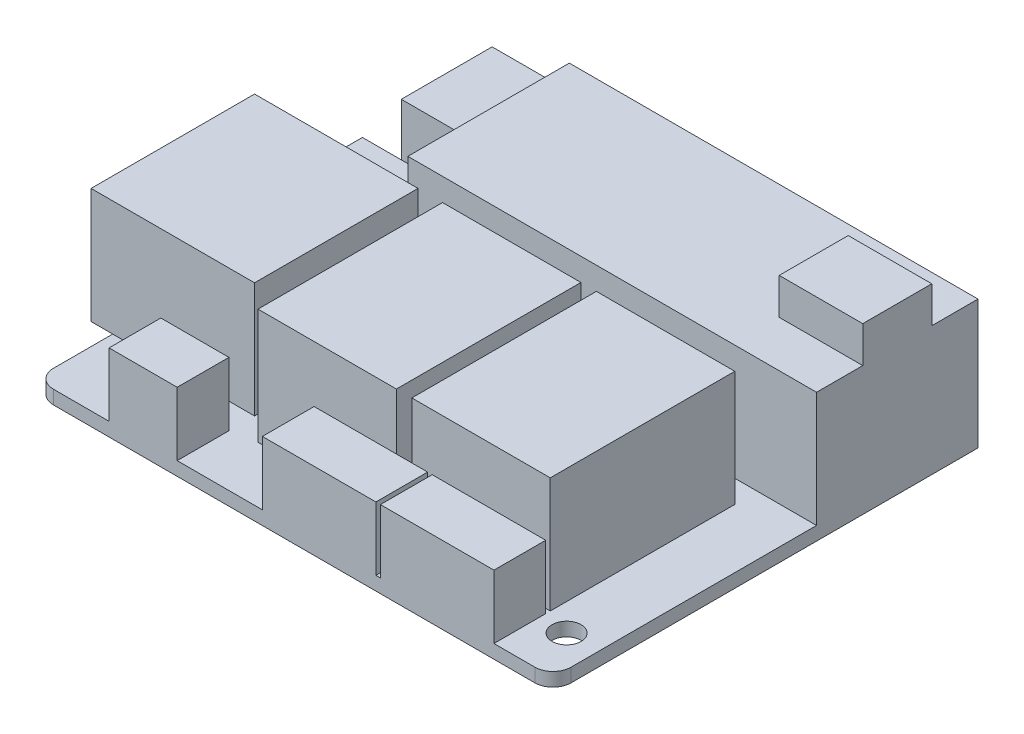
SolidWorks part; units mm, degrees
ref_plane "Front plane" through (0, 0, 0) normal (0, 0, 1) x (1, 0, 0)
ref_plane "Top plane" through (0, 0, 0) normal (0, 1, 0) x (1, 0, 0)
ref_plane "Right Plane" through (0, 0, 0) normal (1, 0, 0) x (0, 0, -1)
sketch "Sketch1" plane through (0, 0, 0) normal (0, 1, 0) x (1, 0, 0)
  line L1 (0, 0) -> (45, 0)
  line L2 (0, 0) -> (0, 17.78)
  line L3 (0, 17.78) -> (45, 17.78)
  line L4 (45, 0) -> (45, 17.78)
  line L5 (38.5, -22.82) -> (23.26, -22.82)
  line L6 (38.5, -22.82) -> (38.5, -2.5)
  line L7 (38.5, -2.5) -> (23.26, -2.5)
  line L8 (23.26, -22.82) -> (23.26, -2.5)
  line L9 (21.56, -22.82) -> (6.32, -22.82)
  line L10 (21.56, -22.82) -> (21.56, -2.5)
  line L11 (21.56, -2.5) -> (6.32, -2.5)
  line L12 (6.32, -22.82) -> (6.32, -2.5)
  line L13 (3.62, -2.5) -> (-14.38, -2.5)
  line L14 (3.62, -2.5) -> (3.62, -20.5)
  line L15 (3.62, -20.5) -> (-14.38, -20.5)
  line L16 (-14.38, -2.5) -> (-14.38, -20.5)
  dimension "D1" = 45
  dimension "D2" = 17.78
  dimension "D3" = 1.7
  dimension "D4" = 2.5
  dimension "D5" = 6.5
  dimension "D6" = 20.32
  dimension "D7" = 15.24
  dimension "D8" = 18
  dimension "D9" = 2.7
extrude "Boss-Extrude1" add sketch "Sketch1" along normal blind 12.7
sketch "Sketch2" plane through (0, 0, 0) normal (0, 1, 0) x (1, 0, 0)
  line L5 (38.5, -22.82) -> (38.5, -2.5) construction
  line L6 (38.5, -23.32) -> (26, -23.32)
  line L7 (38.5, -23.32) -> (38.5, -29.02)
  line L8 (38.5, -29.02) -> (26, -29.02)
  line L9 (26, -23.32) -> (26, -29.02)
  line L10 (25.5, -23.32) -> (13, -23.32)
  line L11 (25.5, -23.32) -> (25.5, -29.02)
  line L12 (25.5, -29.02) -> (13, -29.02)
  line L13 (13, -23.32) -> (13, -29.02)
  line L14 (23.26, -22.82) -> (38.5, -22.82) construction
  line L36 (3.62, -20.5) -> (3.62, -2.5) construction
  line L37 (3.62, -23.32) -> (-3.88, -23.32)
  line L38 (3.62, -23.32) -> (3.62, -29.02)
  line L39 (3.62, -29.02) -> (-3.88, -29.02)
  line L40 (-3.88, -23.32) -> (-3.88, -29.02)
  dimension "D1" = 5.7
  dimension "D2" = 7.5
  dimension "D3" = 0.5
  dimension "D4" = 12.5
  dimension "D5" = 0.5
extrude "Boss-Extrude2" add sketch "Sketch2" along normal blind 7 separate body
sketch "Sketch4" plane through (0, 0, 0) normal (0, 1, 0) x (1, 0, 0)
  line L0 (0, 17.78) -> (0, 0) construction
  line L1 (-3, 7) -> (-12, 7)
  line L2 (-3, 7) -> (-3, -20.5)
  line L3 (-3, -20.5) -> (-12, -20.5)
  line L4 (-12, 7) -> (-12, -20.5)
  line L8 (-14.38, -20.5) -> (3.62, -20.5) construction
  dimension "D1" = 27.5
  dimension "D2" = 12
  dimension "D3" = 9
extrude "Boss-Extrude4" add sketch "Sketch4" along normal blind 5 separate body
sketch "Sketch5" plane through (0, 0, 0) normal (0, 1, 0) x (1, 0, 0)
  line L1 (-1, 17.78) -> (-8.5, 17.78)
  line L2 (-1, 17.78) -> (-1, 7.78)
  line L3 (-1, 7.78) -> (-8.5, 7.78)
  line L4 (-8.5, 17.78) -> (-8.5, 7.78)
  line L8 (0, 17.78) -> (0, 0) construction
  line L9 (45, 17.78) -> (0, 17.78) construction
  dimension "D1" = 7.5
  dimension "D2" = 10
  dimension "D4" = 1
extrude "Boss-Extrude5" add sketch "Sketch5" along normal blind 10 separate body
sketch "Sketch3" plane through (0, 0, 0) normal (0, 1, 0) x (1, 0, 0)
  line L1 (45, 17.78) -> (-12, 17.78)
  line L2 (45, 17.78) -> (45, -29.02)
  line L3 (45, -29.02) -> (-12, -29.02)
  line L4 (-12, 17.78) -> (-12, -29.02)
  line L8 (-12, 7) -> (-12, -20.5) construction
  line L10 (26, -29.02) -> (38.5, -29.02) construction
  line L11 (45, 17.78) -> (0, 17.78) construction
  line L12 (45, 0) -> (45, 17.78) construction
  line L13 (18.5, 8.48) -> (41.5, 8.48) construction
  circle A0 centre (41.5, -24.02) radius 1.6
  circle A1 centre (41.5, 8.48) radius 1.6
  circle A2 centre (18.5, 8.48) radius 1.6
  dimension "D2" = 3.2
  dimension "D1" = 37.5
  dimension "D3" = 3.5
  dimension "D4" = 23
  dimension "D5" = 5
extrude "Boss-Extrude3" add sketch "Sketch3" against normal blind 1.5
sketch "Sketch6" plane through (0, 12.7, 0) normal (0, 1, 0) x (1, 0, 0)
  line L0 (45, 0) -> (45, 17.78) construction
  line L1 (45, 12.69) -> (35.8, 12.69)
  line L2 (45, 12.69) -> (45, 5.09)
  line L3 (45, 5.09) -> (35.8, 5.09)
  line L4 (35.8, 12.69) -> (35.8, 5.09)
  line L5 (0, 17.78) -> (0, 0) construction
  point P6 (35.8, 8.89)
  point P9 (0, 8.89)
  dimension "D1" = 7.6
  dimension "D2" = 9.2
extrude "Boss-Extrude6" add sketch "Sketch6" along normal blind 4
fillet "Fillet1" radius 2 3 edges at (45, -0.75, 29.02) (-12, -0.75, 29.02) (-12, -0.75, -17.78)
